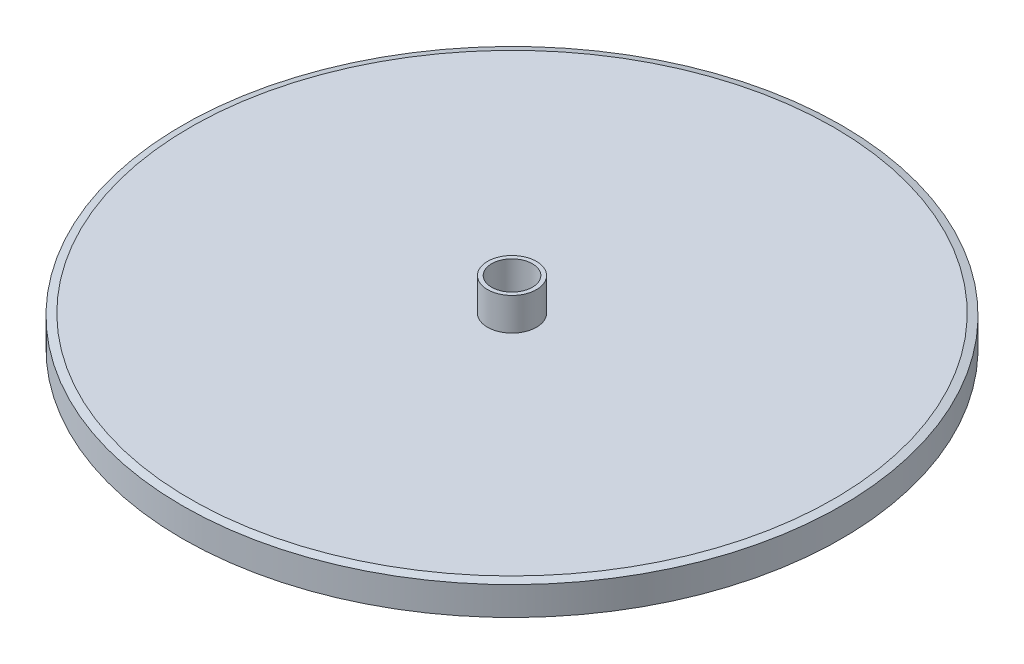
SolidWorks part; units mm, degrees
material "Сталь ШХ15 ГОСТ 801-78"
ref_plane "Plane1" through (0, 0, 0) normal (0, 0, 1) x (1, 0, 0)
ref_plane "Plane2" through (0, 0, 0) normal (0, 1, 0) x (1, 0, 0)
ref_plane "Plane3" through (0, 0, 0) normal (1, 0, 0) x (0, 0, -1)
sketch "Эскиз1" plane through (0, 0, 0) normal (0, 0, 1) x (1, 0, 0)
  line L0 (0, 0) -> (40.4, 0)
  line L1 (40.4, 0) -> (40.4, 4)
  line L2 (40.4, 4) -> (3, 4)
  line L3 (3, 4) -> (3, 8)
  line L4 (3, 8) -> (0, 8)
  line L5 (0, 8) -> (0, 0)
  dimension "D1" = 4
  dimension "30" = 40.4
  dimension "D3" = 3
  dimension "D4" = 4
ref_axis "Ось1" through (0, 8, 0) along (0, -1, 0)
revolve "Повернуть2" add sketch "Эскиз1" angle 360 about axis through (0, 8, 0) along (0, -1, 0)
chamfer "Фаска1" distance 0.94 angle 15 1 edges at (0, 4, 40.4) first distance on face at (0, 4, 3)
chamfer "Фаска2" distance 0.94 angle 15 1 edges at (0, 0, 40.4) first distance on face at (0, 0, 40.4)
sketch "Эскиз2" plane through (0, 0, 0) normal (0, -1, 0) x (-1, 0, 0)
  circle A0 centre (0, 0) radius 2.5
sketch "Эскиз3" plane through (0, 0, 0) normal (0, 0, 1) x (1, 0, 0)
  circle A0 centre (0, 5.828) radius 1
  point P2 (0, 0)
  point P3 (0, 0)
  point P4 (0, 0)
  point P5 (0, 5.828)
  point P6 (0, 0)
  point P11 (0, 0)
  point P12 (0, 0)
  point P13 (0, 0)
extrude "Вырез-Вытянуть3" cut sketch "Эскиз2" against normal through all both contours A0
